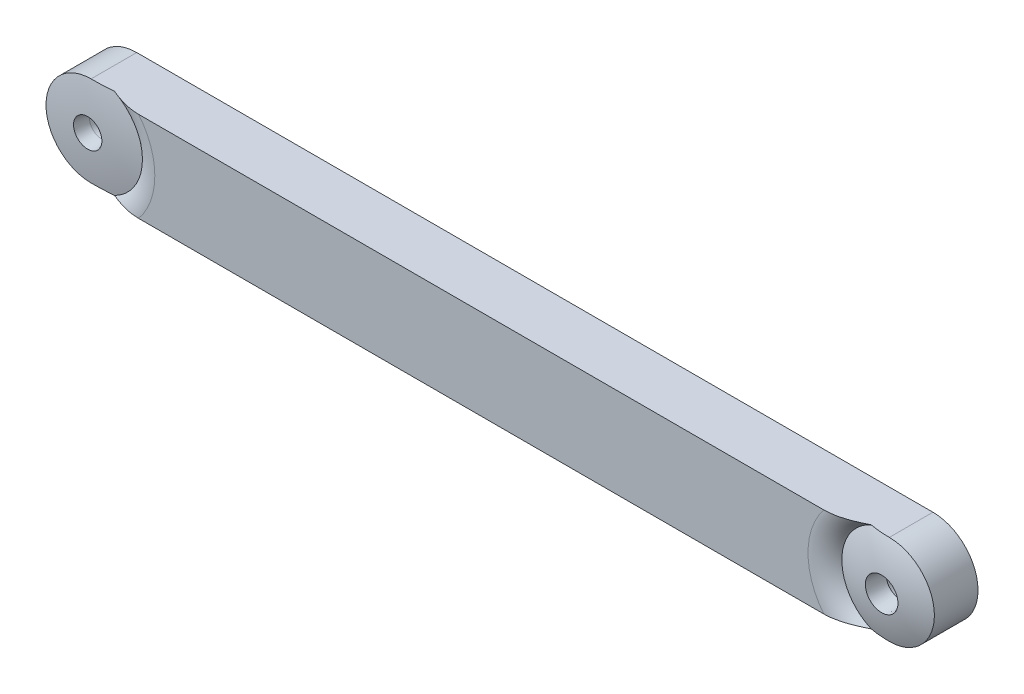
SolidWorks part; units mm, degrees
ref_plane "Спереди" through (0, 0, 0) normal (0, 0, 1) x (1, 0, 0)
ref_plane "Сверху" through (0, 0, 0) normal (0, 1, 0) x (1, 0, 0)
ref_plane "Справа" through (0, 0, 0) normal (1, 0, 0) x (0, 0, -1)
sketch "Эскиз1" plane through (0, 0, 0) normal (0, 0, 1) x (1, 0, 0)
  line L0 (18.5, 95.4938) -> (124.5, 95.4938) construction
  line L2 (18.5, 101.4938) -> (124.5, 101.4938)
  line L3 (18.5, 89.4938) -> (124.5, 89.4938)
  arc A0 (18.5, 101.4938) -> (18.5, 89.4938) centre (18.5, 95.4938) ccw
  arc A1 (124.5, 89.4938) -> (124.5, 101.4938) centre (124.5, 95.4938) ccw
  circle A2 centre (124.5, 95.4938) radius 1.55
  circle A3 centre (18.5, 95.4938) radius 1.55
  point P6 (71.5, 95.4938)
  dimension "D2" = 3.1
  dimension "D3" = 106
  dimension "D1" = 12
extrude "Бобышка-Вытянуть1" add sketch "Эскиз1" along normal blind 7
ref_point "Точка1"
ref_point "Точка2"
ref_axis "Ось1" through (18.5, 95.4938, 14.0928) along (0, 0, -1)
ref_axis "Ось2" through (124.5, 95.4938, 11.9192) along (0, 0, -1)
ref_plane "Плоскость1" through (0, 95.4938, 0) normal (0, 1, 0) x (1, 0, 0)
sketch "Эскиз3" plane through (0, 95.4938, 0) normal (0, 1, 0) x (1, 0, 0)
  line L0 (11.7883, -5.9539) -> (11.5, -7.4986)
  line L1 (1017.0521, -3.6551) -> (-982.9479, -3.6551) construction
  line L2 (16.6162, -6.5263) -> (17.152, -3.6551)
  line L3 (11.5, -7.4986) -> (18.5, -7.4986)
  line L4 (18.5, -14.0928) -> (18.5, 5.9524) construction
  line L5 (18.5, -7.4986) -> (18.5, -3.6551)
  line L7 (16.6162, -0.784) -> (17.152, -3.6551)
  line L9 (18.5, 0.1883) -> (18.5, -3.6551)
  line L10 (15, 0.1883) -> (18.5, 0.1883)
  line L11 (15.101, -0.8937) -> (15, 0.1883)
  arc A1 (11.7883, -5.9539) -> (16.6162, -6.5263) centre (18.5, 30.0114) ccw
  arc A2 (15.101, -0.8937) -> (16.6162, -0.784) centre (18.5, -37.3216) cw
  dimension "D1" = 7
revolve "Вырез-Повернуть1" cut sketch "Эскиз3" angle 360 about axis through (18.5, 95.4938, 14.0928) along (0, 0, -1)
sketch "Эскиз4" plane through (0, 95.4938, 0) normal (0, 1, 0) x (1, 0, 0)
  line L0 (124.5, -6.8295) -> (124.5, -8.8438)
  line L1 (124.6342, -4.3736) -> (129.5552, -4.3736) construction
  line L2 (124.5, -8.8438) -> (131.5, -8.8438)
  line L3 (124.5, -0.9589) -> (124.5, -4.3736)
  line L5 (126.6679, -6.8295) -> (126.3402, -4.3736)
  line L6 (128.6206, 1.0401) -> (128.2614, -1.3768)
  line L8 (131.5, -8.8438) -> (131.0625, -5.565)
  line L9 (124.5, -6.8295) -> (124.5, -4.3736)
  line L10 (126.825, -1.1115) -> (126.3402, -4.3736)
  line L11 (124.5, 1.0401) -> (128.6206, 1.0401)
  line L12 (124.5, -0.9589) -> (124.5, 1.0401)
  arc A0 (126.6679, -6.8295) -> (131.0625, -5.565) centre (124.5, 8.973) ccw
  arc A1 (126.825, -1.1115) -> (128.2614, -1.3768) centre (124.5, -17.7203) cw
  point P1 (0, 0)
  point P3 (131.0777, -5.6745)
  point P6 (0, 0)
  point P8 (126.6679, -6.8295)
  dimension "D2" = 7
revolve "Вырез-Повернуть2" cut sketch "Эскиз4" angle 360 about L9
fillet "Скругление1" radius 4 2 edges at (25.407, 95.4938, 7) (117.746, 95.4938, 7)
